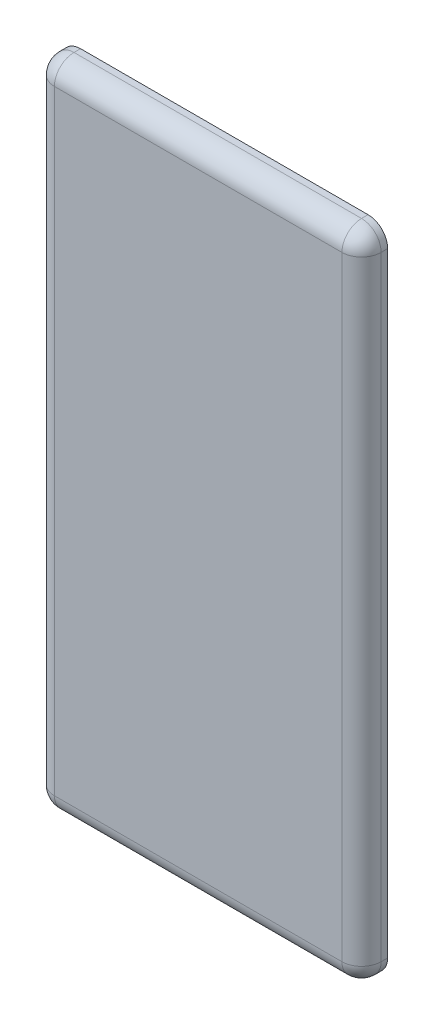
SolidWorks part; units mm, degrees
ref_plane "Top Plane" through (0, 0, 0) normal (0, 0, 1) x (1, 0, 0)
ref_plane "Right Plane" through (0, 0, 0) normal (0, 1, 0) x (1, 0, 0)
ref_plane "Front Plane" through (0, 0, 0) normal (1, 0, 0) x (0, 0, -1)
sketch "Sketch1" plane through (0, 0, 0) normal (0, 0, 1) x (1, 0, 0)
  line L1 (-25, -50) -> (25, -50)
  line L2 (-25, -50) -> (-25, 50)
  line L3 (-25, 50) -> (25, 50)
  line L4 (25, -50) -> (25, 50)
  line L5 (-25, -50) -> (25, 50) construction
  line L6 (-25, 50) -> (25, -50) construction
  point P0 (0, 0)
  dimension "D1" = 100
  dimension "D2" = 50
extrude "Boss-Extrude1" add sketch "Sketch1" along normal blind 4
fillet "Fillet1" radius 3 4 edges at (0, -50, 4) (-25, 0, 4) (0, 50, 4) (25, 0, 4)
fillet "Fillet2" radius 3 8 edges at (-24.1213, 49.1213, 3.1213) (24.1213, 49.1213, 3.1213) (24.1213, -49.1213, 3.1213) (-24.1213, -49.1213, 3.1213) (-25, 50, 0.5) (25, 50, 0.5) (25, -50, 0.5) (-25, -50, 0.5)
sketch "Sketch2" plane through (0, 0, 0) normal (0, 0, -1) x (-1, 0, 0)
  line L0 (0, 25) -> (0, -25) construction
  circle A0 centre (0, 25) radius 4.75
  circle A1 centre (0, -25) radius 4.75
  dimension "D1" = 9.5
  dimension "D2" = 50
extrude "Boss-Extrude2" add sketch "Sketch2" along normal blind 10
chamfer "Chamfer1" distance 3 angle 22 2 edges at (-4.75, -25, -10) (-4.75, 25, -10) first distance on face at (-4.75, -25, -10) first distance on face at (-4.75, 25, -10)
